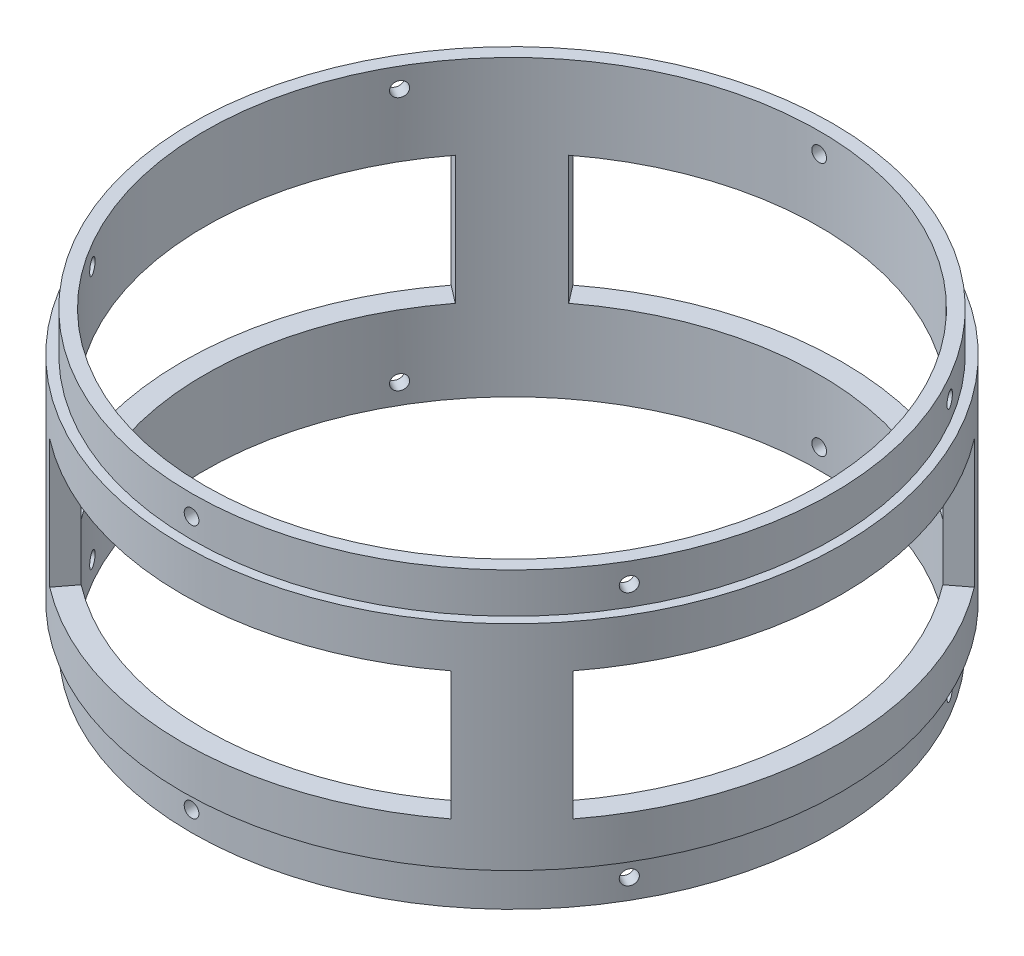
SolidWorks part; units mm, degrees
ref_plane "Front Plane" through (0, 0, 0) normal (0, 0, 1) x (1, 0, 0)
ref_plane "Top Plane" through (0, 0, 0) normal (0, 1, 0) x (1, 0, 0)
ref_plane "Right Plane" through (0, 0, 0) normal (1, 0, 0) x (0, 0, -1)
sketch "Sketch1" plane through (0, 0, 0) normal (0, 1, 0) x (1, 0, 0)
  line L0 (0, 0) -> (-47.7019, 62.1664)
  line L1 (0, 0) -> (47.7019, 62.1664)
  line L2 (0, 0) -> (0, 72.1431) construction
  circle A0 centre (0, 0) radius 78.359
  circle A1 centre (0, 0) radius 73.025
  circle A2 centre (0, 0) radius 76.1746
  dimension "D1" = 156.718
  dimension "D2" = 146.05
  dimension "D3" = 152.3492
  dimension "D4" = 75
extrude "Boss-Extrude1" add sketch "Sketch1" along normal blind 50.8 contours L2 A2 L1 A0 | L2 A1 L1 A2 | L2 A2 L1 A1 | L2 A0 L1 A2 | A2 L2 A1 L0 | A0 L2 A2 L0 | A2 L2 A0 L0 | A1 L2 A2 L0 region at (-33.2032, 0, 67.3294) region at (-44.6636, 0, -59.7594) region at (-34.6222, 0, 70.2068) region at (-46.2669, 0, -61.8908)
ref_plane "Plane1" through (0, 25.4, 0) normal (0, 1, 0) x (1, 0, 0)
extrude "Boss-Extrude2" add sketch "Sketch1<3>" along normal blind 9.525 from surface contours A2 L2 A1 L0 | L2 A2 L1 A1 | L2 A1 L1 A2 | A1 L2 A2 L0 region at (-33.2032, 0, 67.3294) region at (-44.6636, 0, -59.7594) starting at face at (0, 50.8, 73.025)
sketch "Sketch1<3>" plane through (0, 0, 0) normal (0, 1, 0) x (1, 0, 0) same geometry as "Sketch1"
extrude "Boss-Extrude3" add sketch "Sketch1<4>" against normal blind 9.525 contours A2 L2 A1 L0 | A1 L2 A2 L0 | L2 A1 L1 A2 | L2 A2 L1 A1 region at (-33.2032, 0, 67.3294) region at (-44.6636, 0, -59.7594)
sketch "Sketch1<4>" plane through (0, 0, 0) normal (0, 1, 0) x (1, 0, 0) same geometry as "Sketch1"
ref_plane "Plane2" through (0, 0, -76.1746) normal (0, 0, -1) x (-1, 0, 0)
ref_axis "Axis1" through (0, 0, 0) along (0, 1, 0)
sketch "Sketch3" plane through (0, 0, -76.1746) normal (0, 0, -1) x (-1, 0, 0)
  line L0 (76.1746, 0) -> (-76.1746, 0) construction
  line L1 (-76.1746, -9.525) -> (76.1746, -9.525) construction
  line L2 (76.1746, 50.8) -> (-76.1746, 50.8) construction
  line L3 (76.1746, 60.325) -> (-76.1746, 60.325) construction
  line L4 (76.1746, 0) -> (-76.1746, 0)
  line L5 (-76.1746, -9.525) -> (76.1746, -9.525)
  line L6 (76.1746, 50.8) -> (-76.1746, 50.8)
  line L7 (76.1746, 60.325) -> (-76.1746, 60.325)
  line L8 (0, 60.325) -> (0, 50.8)
  line L9 (0, 0) -> (0, -9.525)
  circle A0 centre (0, 55.5625) radius 1.75
  circle A1 centre (0, -4.7625) radius 1.75
  point P12 (0, 55.5625)
  point P13 (0, -4.7625)
  point P14 (-77.5445, 179.1871)
  dimension "D1" = 3.5
extrude "Cut-Extrude2" cut sketch "Sketch3" against normal up to next contours L8 A0 | L8 A0 | L9 A1 | L9 A1 region at (-0.7427, 55.5625, -76.1746) region at (0.7427, 55.5625, -76.1746) region at (-0.7427, -4.7625, -76.1746) region at (0.7427, -4.7625, -76.1746)
extrude "Cut-Extrude3" cut sketch "Sketch1<7>" against normal blind 15.24 and the other way blind 15.24 from surface contours L2 A1 L1 A2 | A1 L2 A2 L0 | A2 L2 A0 L0 | L2 A2 L1 A0 region at (-44.6636, 0, -59.7594) region at (-46.2669, 0, -61.8908) starting at plane "Plane1"
sketch "Sketch1<7>" plane through (0, 0, 0) normal (0, 1, 0) x (1, 0, 0) same geometry as "Sketch1"
pattern_circular "CirPattern2" count 4 over 360 about axis through (0, 0, 0) along (0, 1, 0) of "Cut-Extrude3"
pattern_circular "CirPattern3" count 6 over 360 about axis through (0, 0, 0) along (0, 1, 0) of "Cut-Extrude2"
equation "\"AB_Coupler_OD_Length\"= 2in"
equation "\"AB_Coupling_Section_Length\"= 0.375in"
equation "\"AB_Coupler_Length\"= \"AB_Coupler_OD_Length\" + \"AB_Coupling_Section_Length\" * 2"
equation "\"D1@Boss-Extrude2\"=\"AB_Coupling_Section_Length\""
equation "\"D1@Boss-Extrude3\"=\"AB_Coupling_Section_Length\""
equation "\"D1@Boss-Extrude1\" = \"AB_Coupler_OD_Length\""
equation "\"Cutout_Angle\" = 75"
equation "\"AB_Coupler_Num_Screws\"= 6"
equation "\"Num_Cutouts\" = 4"
equation "\"D4@Sketch1\"=\"Cutout_Angle\""
equation "\"D1@CirPattern2\"=\"Num_Cutouts\""
equation "\"D1@CirPattern3\"=\"AB_Coupler_Num_Screws\""
equation "\"AB_Coupler_OD\" = 6.17in"
equation "\"AB_Coupler_ID\"= 5.75in"
equation "\"AB_Coupler_Surface_Diameter\"= 5.998in"
equation "\"D3@Sketch1\"=\"AB_Coupler_Surface_Diameter\""
equation "\"D2@Sketch1\"=\"AB_Coupler_ID\""
equation "\"D1@Sketch1\"=\"AB_Coupler_OD\""
equation "\"AB_Coupling_Screw_Diameter\"= 3.5mm"
equation "\"Aft_Section_Length\"= 40in"
equation "\"Aft_Lower_Length\"= 20in"
equation "\"Aft_Upper_Length\"= \"Aft_Section_Length\" - \"Aft_Lower_Length\" - \"AB_Coupler_OD_Length\""
